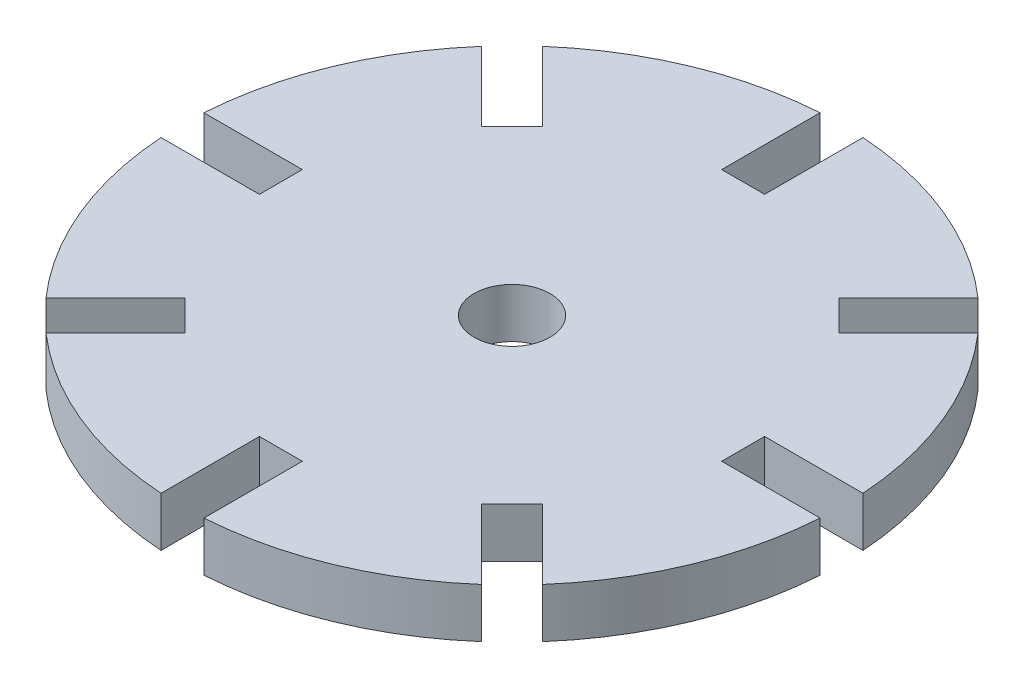
SolidWorks part; units mm, degrees
ref_plane "Front Plane" through (0, 0, 0) normal (0, 0, 1) x (1, 0, 0)
ref_plane "Top Plane" through (0, 0, 0) normal (0, 1, 0) x (1, 0, 0)
ref_plane "Right Plane" through (0, 0, 0) normal (1, 0, 0) x (0, 0, -1)
ref_axis "Axis1" through (0, 1.7463, 0) along (0, -1, 0)
sketch "Sketch1" plane through (0, 0, 0) normal (0, 1, 0) x (1, 0, 0)
  circle A0 centre (0, 0) radius 2.3
  circle A1 centre (0, 0) radius 20
  dimension "D1" = 4.6
  dimension "D2" = 40
extrude "Boss-Extrude1" add sketch "Sketch1" along normal blind 1.5 and the other way blind 1.5
sketch "Sketch2" plane through (0, 1.5, 0) normal (0, 1, 0) x (1, 0, 0)
  line L1 (26, -1.3) -> (14, -1.3)
  line L2 (26, -1.3) -> (26, 1.3)
  line L3 (26, 1.3) -> (14, 1.3)
  line L4 (14, -1.3) -> (14, 1.3)
  line L5 (20, 1.3) -> (20, -1.3) construction
  line L6 (26, 0) -> (14, 0) construction
  line L7 (3.6213, -1.5) -> (3.6213, 1.5) construction
  line L8 (3.6213, 1.5) -> (1.5, 3.6213) construction
  line L9 (1.5, 3.6213) -> (-1.5, 3.6213) construction
  line L10 (-1.5, 3.6213) -> (-3.6213, 1.5) construction
  line L11 (-3.6213, 1.5) -> (-3.6213, -1.5) construction
  line L12 (-3.6213, -1.5) -> (-1.5, -3.6213) construction
  line L13 (-1.5, -3.6213) -> (1.5, -3.6213) construction
  line L14 (1.5, -3.6213) -> (3.6213, -1.5) construction
  circle A0 centre (0, 0) radius 20 construction
  circle A1 centre (0, 0) radius 3.6213 construction
  point P0 (20, 0)
  dimension "D1" = 2.6
  dimension "D2" = 6
  dimension "D3" = 3
extrude "Cut-Extrude1" cut sketch "Sketch2" against normal through all
pattern_circular "CirPattern1" count 8 over 360 about axis through (0, 1.7463, 0) along (0, -1, 0) of "Cut-Extrude1"
